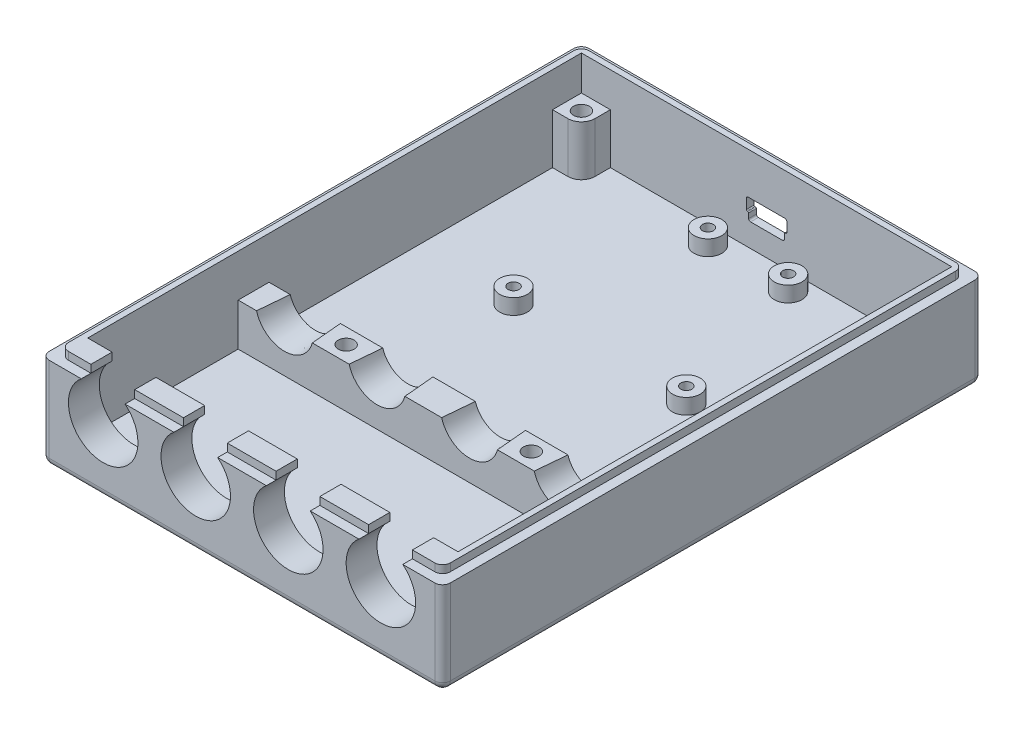
SolidWorks part; units mm, degrees
ref_plane "Front Plane" through (0, 0, 0) normal (0, 0, 1) x (1, 0, 0)
ref_plane "Top Plane" through (0, 0, 0) normal (0, 1, 0) x (1, 0, 0)
ref_plane "Right Plane" through (0, 0, 0) normal (1, 0, 0) x (0, 0, -1)
sketch "Sketch1" plane through (0, 0, 0) normal (0, 1, 0) x (1, 0, 0)
  line L1 (-41.275, -55.5625) -> (41.275, -55.5625)
  line L2 (-41.275, -55.5625) -> (-41.275, 55.5625)
  line L3 (-41.275, 55.5625) -> (41.275, 55.5625)
  line L4 (41.275, -55.5625) -> (41.275, 55.5625)
  line L5 (-41.275, -55.5625) -> (41.275, 55.5625) construction
  line L6 (-41.275, 55.5625) -> (41.275, -55.5625) construction
  point P0 (0, 0)
  dimension "D1" = 82.55
  dimension "D2" = 111.125
extrude "Boss-Extrude1" add sketch "Sketch1" along normal blind 19.05
sketch "Sketch11" plane through (0, 0, 55.5625) normal (0, 0, 1) x (1, 0, 0)
  line L0 (0, 19.05) -> (0, 6.35) construction
  line L1 (-41.275, 19.05) -> (41.275, 19.05) construction
  line L2 (-41.275, 6.35) -> (41.275, 6.35) construction
  line L3 (-41.275, 19.05) -> (-41.275, 0) construction
  line L4 (41.275, 19.05) -> (41.275, 0) construction
  circle A0 centre (-28.575, 13.5001) radius 7.1501
  circle A1 centre (-9.525, 13.5001) radius 7.1501
  circle A2 centre (9.525, 13.5001) radius 7.1501
  circle A3 centre (28.575, 13.5001) radius 7.1501
  point P11 (-38.1, 6.35)
  point P12 (-28.575, 6.35)
  point P13 (-9.525, 6.35)
  point P14 (9.525, 6.35)
  point P15 (28.575, 6.35)
  point P16 (38.1, 6.35)
  point P17 (-28.575, 20.6502)
  point P18 (-9.525, 20.6502)
  point P19 (9.525, 20.6502)
  point P20 (28.575, 20.6502)
  dimension "D1" = 12.7
  dimension "D2" = 3.175
  dimension "D3" = 9.525
  dimension "D4" = 19.05
  dimension "D5" = 19.05
  dimension "D6" = 19.05
  dimension "D7" = 3.175
  dimension "D8" = 9.525
  dimension "D9" = 14.3002
  dimension "D10" = 14.3002
  dimension "D11" = 14.3002
  dimension "D12" = 14.3002
sketch "Sketch14" plane through (0, 19.05, 0) normal (0, 1, 0) x (-1, 0, 0)
  line L0 (0, 0) -> (0, -1.5875) construction
  line L3 (38.1, 49.2125) -> (-38.1, 49.2125)
  line L4 (38.1, 49.2125) -> (38.1, -52.3875)
  line L5 (38.1, -52.3875) -> (-38.1, -52.3875)
  line L6 (-38.1, 49.2125) -> (-38.1, -52.3875)
  line L7 (38.1, 49.2125) -> (-38.1, -52.3875) construction
  line L8 (38.1, -52.3875) -> (-38.1, 49.2125) construction
  dimension "D1" = 1.5875
  dimension "D2" = 101.6
  dimension "D3" = 76.2
extrude "Cut-Extrude3" cut sketch "Sketch14" against normal offset from surface (15.875 mm away) 3.175 up to face at (0, 0, 0)
extrude "Cut-Extrude4" cut sketch "Sketch11" against normal up to next
sketch "Sketch16" plane through (0, 0, 49.2125) normal (0, 0, -1) x (-1, 0, 0)
  point P0 (28.575, 13.5001)
  point P1 (-28.575, 13.5001)
sketch3d "ControllerCenter"
sketch "Sketch17" plane through (0, 3.175, 0) normal (0, 1, 0) x (-1, 0, 0)
  line L0 (0, 49.2125) -> (0, 18.2562) construction
  line L1 (5.0169, 49.2125) -> (-5.0169, 49.2125) construction
  line L2 (38.1, 18.2562) -> (-38.1, 18.2562)
  line L3 (38.1, 18.2562) -> (38.1, 11.9062)
  line L4 (-38.1, 18.2562) -> (-38.1, 11.9062)
  line L5 (38.1, 11.9062) -> (-38.1, 11.9062)
  line L6 (38.1, -52.3875) -> (38.1, 49.2125) construction
  line L7 (-38.1, 49.2125) -> (-38.1, -52.3875) construction
  line L8 (0, -52.3875) -> (0, 11.9062) construction
  line L9 (-38.1, -52.3875) -> (38.1, -52.3875) construction
  line L10 (32.1469, -49.2125) -> (32.1469, -52.3875)
  line L11 (-38.1, -52.3875) -> (38.1, -52.3875) construction
  line L12 (34.925, -46.4344) -> (38.1, -46.4344)
  line L13 (38.1, -52.3875) -> (32.1469, -52.3875)
  line L14 (-32.1469, -49.2125) -> (-32.1469, -52.3875)
  line L15 (-34.925, -46.4344) -> (-38.1, -46.4344)
  line L16 (-38.1, -46.4344) -> (-38.1, -52.3875)
  line L17 (-38.1, -52.3875) -> (-32.1469, -52.3875)
  line L18 (38.1, -46.4344) -> (38.1, -52.3875)
  arc A0 (34.925, -46.4344) -> (32.1469, -49.2125) centre (34.925, -49.2125) ccw
  arc A1 (-34.925, -46.4344) -> (-32.1469, -49.2125) centre (-34.925, -49.2125) cw
  dimension "D5" = 5.5562
  dimension "D1" = 30.9562
  dimension "D2" = 6.35
  dimension "D3" = 3.175
  dimension "D4" = 3.175
extrude "Boss-Extrude4" add sketch "Sketch17" along normal up to surface (10.3251 mm away)
sketch "Sketch18" plane through (0, 0, 18.2562) normal (0, 0, 1) x (1, 0, 0)
  line L0 (-38.1, 13.5001) -> (38.1, 13.5001) construction
  circle A0 centre (-28.575, 13.5001) radius 5.9531
  circle A1 centre (-9.525, 13.5001) radius 5.9531
  circle A2 centre (9.525, 13.5001) radius 5.9531
  circle A3 centre (28.575, 13.5001) radius 5.9531
  point P0 (-28.575, 13.5001)
  point P1 (-9.525, 13.5001)
  point P4 (9.525, 13.5001)
  point P5 (28.575, 13.5001)
  dimension "D6" = 11.9062
  dimension "D7" = 11.9062
  dimension "D8" = 11.9062
  dimension "D9" = 11.9062
  dimension "D1" = 9.525
  dimension "D2" = 19.05
  dimension "D3" = 19.05
  dimension "D4" = 19.05
  dimension "D5" = 9.525
extrude "Cut-Extrude5" cut sketch "Sketch18" against normal up to next (6.35 mm away) draft 5
sketch "Sketch19" plane through (0, 3.175, 0) normal (0, 1, 0) x (-1, 0, 0)
  line L0 (38.1, -17.2641) -> (-38.1, -17.2641) construction
  line L1 (38.1, -46.4344) -> (38.1, 11.9062) construction
  line L2 (-38.1, 11.9062) -> (-38.1, -46.4344) construction
  line L3 (8.255, -52.3875) -> (8.255, 11.9062) construction
  line L4 (-38.1, -52.3875) -> (38.1, -52.3875) construction
  line L5 (-38.1, 11.9062) -> (38.1, 11.9062) construction
  line L6 (-8.255, -52.3875) -> (-8.255, 11.9062) construction
  line L7 (-32.1469, -52.3875) -> (32.1469, -52.3875) construction
  circle A0 centre (8.255, -48.5775) radius 2.8575
  circle A1 centre (-8.255, -48.5775) radius 2.8575
  circle A2 centre (17.78, -18.0975) radius 2.8575
  circle A3 centre (-17.78, -18.0975) radius 2.8575
  point P6 (8.255, -17.2641)
  point P7 (-8.255, -17.2641)
  point P18 (8.255, -48.5775)
  point P19 (-8.255, -48.5775)
  point P20 (8.255, -18.0975)
  point P21 (-8.255, -18.0975)
  dimension "D7" = 5.715
  dimension "D8" = 5.715
  dimension "D9" = 9.525
  dimension "D10" = 9.525
  dimension "D11" = 5.715
  dimension "D12" = 5.715
  dimension "D1" = 16.51
  dimension "D2" = 29.845
  dimension "D3" = 3.81
  dimension "D4" = 3.81
  dimension "D5" = 30.48
  dimension "D6" = 30.48
sketch "Sketch21" plane through (0, 0, -55.5625) normal (0, 0, -1) x (-1, 0, 0)
  line L0 (0, 19.05) -> (0, 0) construction
  line L1 (-41.275, 19.05) -> (41.275, 19.05) construction
  line L2 (0, 7.9375) -> (3.683, 7.9375) construction
  line L3 (-3.683, 7.9375) -> (-3.683, 9.525)
  line L4 (-3.683, 7.9375) -> (3.683, 7.9375)
  line L5 (-3.683, 9.525) -> (-4.1672, 9.525)
  line L6 (4.1672, 9.525) -> (4.1672, 12.1047)
  line L7 (-4.1672, 12.1047) -> (4.1672, 12.1047)
  line L8 (-4.1672, 9.525) -> (-4.1672, 12.1047)
  line L9 (-4.1672, 12.1047) -> (4.1672, 7.9375) construction
  line L10 (-4.1672, 7.9375) -> (4.1672, 12.1047) construction
  line L14 (3.683, 7.9375) -> (3.683, 9.525)
  line L15 (3.683, 9.525) -> (4.1672, 9.525)
  point P11 (0, 12.1047)
  point P13 (0, 10.0211)
  dimension "D1" = 4.1672
  dimension "D2" = 3.683
  dimension "D3" = 1.5875
  dimension "D4" = 2.5797
extrude "Cut-Extrude7" cut sketch "Sketch21" against normal up to next
fillet "Fillet6" radius 1.5875 8 edges at (-41.275, 0, 0) (-41.275, 9.525, -55.5625) (0, 0, -55.5625) (41.275, 9.525, -55.5625) (41.275, 0, 0) (0, 0, 55.5625) (41.275, 9.525, 55.5625) (-41.275, 9.525, 55.5625)
sketch "Sketch25" plane through (0, 0, -52.3875) normal (0, 0, 1) x (1, 0, 0)
  line L0 (-5.2218, 3.175) -> (-5.2218, 19.05) construction
  line L1 (32.1469, 3.175) -> (-32.1469, 3.175) construction
  line L2 (38.1, 19.05) -> (-38.1, 19.05) construction
  point P4 (-5.2218, 6.35)
  point P7 (-5.2218, 7.9375)
  dimension "D1" = 3.175
  dimension "D2" = 1.5875
sketch3d "BoardTop"
extrude "Boss-Extrude8" add sketch "Sketch19" along normal offset from surface (3.175 mm away) 1.5875
sketch "HoleLocations" plane through (0, 13.5001, 0) normal (0, 1, 0) x (-1, 0, 0)
  point P0 (19.05, 15.0812)
  point P1 (-19.05, 15.0812)
  point P2 (34.925, -49.2125)
  point P3 (-34.925, -49.2125)
sketch "HoleLocationsUnder" plane through (0, 0, 0) normal (0, -1, 0) x (1, 0, 0)
  point P0 (-19.05, 15.0812)
  point P1 (19.05, 15.0812)
hole_wizard "CBORE for #4 Pan Head Machine Screw3" positions "Sketch34" profile "Sketch35" counterbore size "#4" standard "Ansi Inch" end condition through all
sketch "Sketch34" plane through (0, 0, 0) normal (0, -1, 0) x (1, 0, 0)
  point P0 (-19.05, 15.0812)
  point P4 (19.05, 15.0812)
  point P7 (-34.925, -49.2125)
  point P10 (34.925, -49.2125)
sketch "Sketch35" plane through (-19.05, 0, 15.0812) normal (1, 0, 0) x (0, 0, -1)
  line L0 (0, 0) -> (0, 19.05)
  line L1 (0, 19.05) -> (1.6319, 19.05)
  line L3 (1.6319, 19.05) -> (1.632, 2.032)
  line L4 (1.632, 2.032) -> (3.175, 2.032)
  line L5 (3.175, 2.032) -> (3.175, 0)
  line L7 (3.175, 0) -> (0, 0)
  line L11 (0, -6.35) -> (0, 107.95) construction
  dimension "Thru Hole Dia." = 3.2639
  dimension "Thru Hole Depth" = 19.05
  dimension "C'Bore Dia." = 6.35
  dimension "C'Bore Depth" = 2.032
hole_wizard "#4-40 Tapped Hole1" positions "Sketch37" profile "Sketch38" tap size "#4-40" standard "Ansi Inch"
sketch "Sketch37" plane through (-31.8238, 6.35, 11.9974) normal (0, 1, 0) x (-1, 0, 0)
  point P0 (-23.5688, -60.5749)
  point P4 (-14.0438, -30.0949)
  point P7 (-49.6038, -30.0949)
  point P10 (-40.0788, -60.5749)
sketch "Sketch38" plane through (-8.255, 6.35, -48.5775) normal (1, 0, 0) x (0, 0, 1)
  line L0 (0, 0) -> (0, 5.4544)
  line L1 (0, 5.4544) -> (1.1303, 4.7752)
  line L2 (1.1303, 4.7752) -> (1.1303, 0)
  line L5 (1.1303, 0) -> (0, 0)
  line L10 (0, 5.4544) -> (-1.1303, 4.7752) construction
  line L11 (0, -6.35) -> (0, 107.95) construction
  dimension "Tap Drill Dia." = 2.2606
  dimension "Tap Drill Depth" = 4.7752
  dimension "Drill Angle" = 118
cosmetic thread "Hole Thread1" parameters "D1"=4.7752, "D2"=2.8448
cosmetic thread "Hole Thread2" parameters "D1"=4.7752, "D2"=2.8448
cosmetic thread "Hole Thread3" parameters "D1"=4.7752, "D2"=2.8448
cosmetic thread "Hole Thread4" parameters "D1"=4.7752, "D2"=2.8448
sketch "Sketch39" plane through (0, 0, -55.5625) normal (0, 0, -1) x (-1, 0, 0)
  line L0 (-4.1672, 12.1047) -> (4.1672, 7.9375) construction
  line L1 (4.1672, 12.1047) -> (-4.1672, 7.9375) construction
  line L3 (-8.7312, 2.8773) -> (8.7313, 2.8773)
  line L4 (-8.7312, 2.8773) -> (-8.7312, 17.1648)
  line L5 (-8.7312, 17.1648) -> (8.7313, 17.1648)
  line L6 (8.7313, 2.8773) -> (8.7313, 17.1648)
  line L7 (-8.7312, 2.8773) -> (8.7313, 17.1648) construction
  line L8 (-8.7312, 17.1648) -> (8.7313, 2.8773) construction
  point P6 (0, 10.0211)
  dimension "D1" = 14.2875
  dimension "D2" = 17.4625
extrude "Cut-Extrude8" cut sketch "Sketch39" against normal blind 1.5875
fillet "Fillet7" radius 0.7937 4 edges at (8.7312, 2.8773, -54.7688) (-8.7313, 2.8773, -54.7688) (-8.7313, 17.1648, -54.7688) (8.7312, 17.1648, -54.7688)
fillet "Fillet8" radius 0.1984 4 edges at (-4.1672, 9.525, -53.1813) (-3.683, 9.525, -53.1813) (4.1672, 9.525, -53.1813) (3.683, 9.525, -53.1813)
fillet "Fillet9" radius 0.3969 4 edges at (3.683, 7.9375, -53.1813) (-3.683, 7.9375, -53.1813) (-4.1672, 12.1047, -53.1813) (4.1672, 12.1047, -53.1813)
sketch "Sketch40" plane through (0, 19.05, 0) normal (0, 1, 0) x (1, 0, 0)
  line L0 (-33.0831, -49.2125) -> (-33.0831, -53.5781)
  line L1 (-33.0831, -49.2125) -> (-33.0831, -55.5625) construction
  line L2 (-33.0831, -49.2125) -> (-38.1, -49.2125)
  line L3 (39.6875, 55.5625) -> (-39.6875, 55.5625) construction
  line L4 (-39.2906, 53.5781) -> (39.2906, 53.5781)
  line L5 (-39.2906, 53.5781) -> (-39.2906, -53.5781)
  line L6 (-39.2906, -53.5781) -> (-33.0831, -53.5781)
  line L7 (39.2906, 53.5781) -> (39.2906, -53.5781)
  line L8 (-41.275, 53.975) -> (-41.275, -53.975) construction
  line L9 (41.275, -53.975) -> (41.275, 53.975) construction
  line L10 (-39.6875, -55.5625) -> (-33.0831, -55.5625) construction
  line L11 (-38.1, -49.2125) -> (-38.1, 52.3875)
  line L12 (-38.1, 52.3875) -> (38.1, 52.3875)
  line L13 (38.1, 52.3875) -> (38.1, -49.2125)
  line L14 (38.1, -49.2125) -> (33.0831, -49.2125)
  line L15 (33.0831, -49.2125) -> (33.0831, -53.5781)
  line L16 (33.0831, -55.5625) -> (33.0831, -49.2125) construction
  line L17 (-24.0669, -49.2125) -> (-24.0669, -53.5781)
  line L18 (-24.0669, -55.5625) -> (-24.0669, -49.2125) construction
  line L19 (-14.0331, -49.2125) -> (-14.0331, -53.5781)
  line L20 (-14.0331, -49.2125) -> (-14.0331, -55.5625) construction
  line L21 (-24.0669, -49.2125) -> (-14.0331, -49.2125)
  line L22 (-5.0169, -49.2125) -> (-5.0169, -53.5781)
  line L23 (-5.0169, -55.5625) -> (-5.0169, -49.2125) construction
  line L24 (5.0169, -49.2125) -> (5.0169, -53.5781)
  line L25 (5.0169, -49.2125) -> (5.0169, -55.5625) construction
  line L26 (-5.0169, -49.2125) -> (5.0169, -49.2125)
  line L27 (14.0331, -49.2125) -> (14.0331, -53.5781)
  line L28 (14.0331, -55.5625) -> (14.0331, -49.2125) construction
  line L29 (24.0669, -49.2125) -> (24.0669, -53.5781)
  line L30 (24.0669, -49.2125) -> (24.0669, -55.5625) construction
  line L31 (14.0331, -49.2125) -> (24.0669, -49.2125)
  line L32 (-24.0669, -53.5781) -> (-14.0331, -53.5781)
  line L33 (-5.0169, -53.5781) -> (5.0169, -53.5781)
  line L34 (14.0331, -53.5781) -> (24.0669, -53.5781)
  line L35 (33.0831, -53.5781) -> (39.2906, -53.5781)
  dimension "D1" = 1.9844
  dimension "D2" = 1.9844
  dimension "D3" = 1.9844
  dimension "D4" = 1.9844
extrude "Boss-Extrude9" add sketch "Sketch40" along normal blind 1.5875
fillet "Fillet10" radius 1.5875 4 edges at (-39.2906, 19.8438, -53.5781) (-39.2906, 19.8438, 53.5781) (39.2906, 19.8438, -53.5781) (39.2906, 19.8438, 53.5781)
sketch "Sketch41" plane through (0, 13.5001, 0) normal (0, 1, 0) x (1, 0, 0)
  line L1 (-38.1, -11.9062) -> (38.1, -11.9062)
  line L2 (-38.1, -11.9062) -> (-38.1, -18.2562)
  line L3 (-38.1, -18.2562) -> (38.1, -18.2562)
  line L4 (38.1, -11.9062) -> (38.1, -18.2562)
extrude "Cut-Extrude9" cut sketch "Sketch41" against normal blind 1.5875
